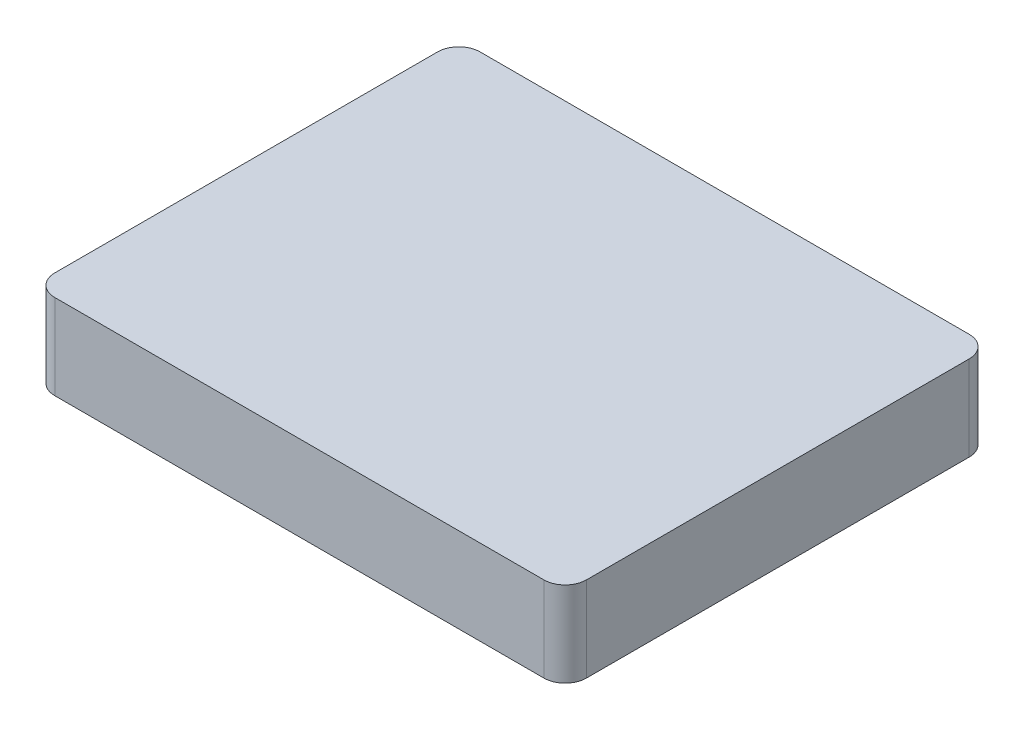
SolidWorks part; units mm, degrees
ref_plane "Front Plane" through (0, 0, 0) normal (0, 0, 1) x (1, 0, 0)
ref_plane "Top Plane" through (0, 0, 0) normal (0, 1, 0) x (1, 0, 0)
ref_plane "Right Plane" through (0, 0, 0) normal (1, 0, 0) x (0, 0, -1)
sketch "Sketch1" plane through (0, 0, 0) normal (0, 1, 0) x (1, 0, 0)
  line L0 (0, 0) -> (15.875, 0)
  line L1 (15.875, 0) -> (15.875, 12.7)
  line L2 (15.875, 12.7) -> (0, 12.7)
  line L3 (0, 12.7) -> (0, 0)
  dimension "D1" = 15.875
  dimension "D2" = 12.7
extrude "Boss-Extrude1" add sketch "Sketch1" along normal blind 2.54
fillet "Fillet1" radius 0.635 4 edges at (0, 1.27, -12.7) (15.875, 1.27, -12.7) (15.875, 1.27, 0) (0, 1.27, 0)
shell "Shell1" thickness 0.635 removed face at (7.9375, 0, -6.35)
sketch "Sketch2" plane through (0, 1.905, 0) normal (0, -1, 0) x (-1, 0, 0)
  line L0 (-0.635, 6.35) -> (-15.24, 6.35) construction
  line L1 (-0.635, 12.065) -> (-0.635, 0.635) construction
  line L2 (-15.24, 0.635) -> (-15.24, 12.065) construction
  line L3 (-7.9375, 0.635) -> (-7.9375, 12.065) construction
  line L4 (-0.635, 0.635) -> (-15.24, 0.635) construction
  line L5 (-15.24, 12.065) -> (-0.635, 12.065) construction
  circle A0 centre (-7.9375, 6.35) radius 2.54
  dimension "D1" = 5.08
extrude "Boss-Extrude2" add sketch "Sketch2" along normal up to surface (1.905 mm away) up to face at (7.9375, 0, -6.35)
